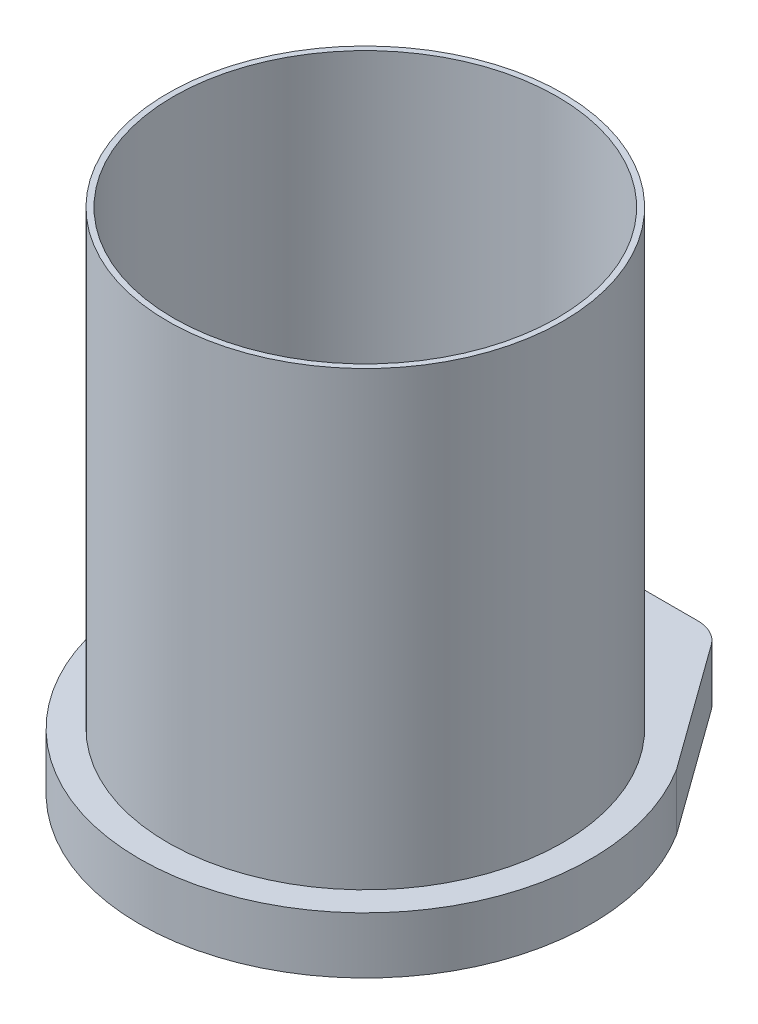
SolidWorks part; units mm, degrees
ref_plane "Спереди" through (0, 0, 0) normal (0, 0, 1) x (1, 0, 0)
ref_plane "Сверху" through (0, 0, 0) normal (0, 1, 0) x (1, 0, 0)
ref_plane "Справа" through (0, 0, 0) normal (1, 0, 0) x (0, 0, -1)
sketch "Эскиз1" plane through (0, 0, 0) normal (0, 1, 0) x (1, 0, 0)
  circle A0 centre (0, 0) radius 170
extrude "Вытянуть-Тонкостенный1" add sketch "Эскиз1" along normal blind 400 thin thin type one direction wall 5
sketch "Эскиз2" plane through (0, 0, 0) normal (0, -1, 0) x (1, 0, 0)
  line L0 (-64.6743, -230) -> (64.6678, -230)
  line L1 (88.9815, -217.5739) -> (169.425, -106.2787)
  line L2 (-168.9828, -106.9804) -> (-88.982, -217.5823)
  arc A0 (-168.9828, -106.9804) -> (169.425, -106.2787) centre (0, 0) cw
  arc A1 (64.6678, -230) -> (88.9815, -217.5739) centre (64.6678, -200) ccw
  arc A2 (-64.6743, -230) -> (-88.982, -217.5823) centre (-64.6743, -200) cw
  dimension "D1" = 30
extrude "Бобышка-Вытянуть1" add sketch "Эскиз2" along normal blind 50
